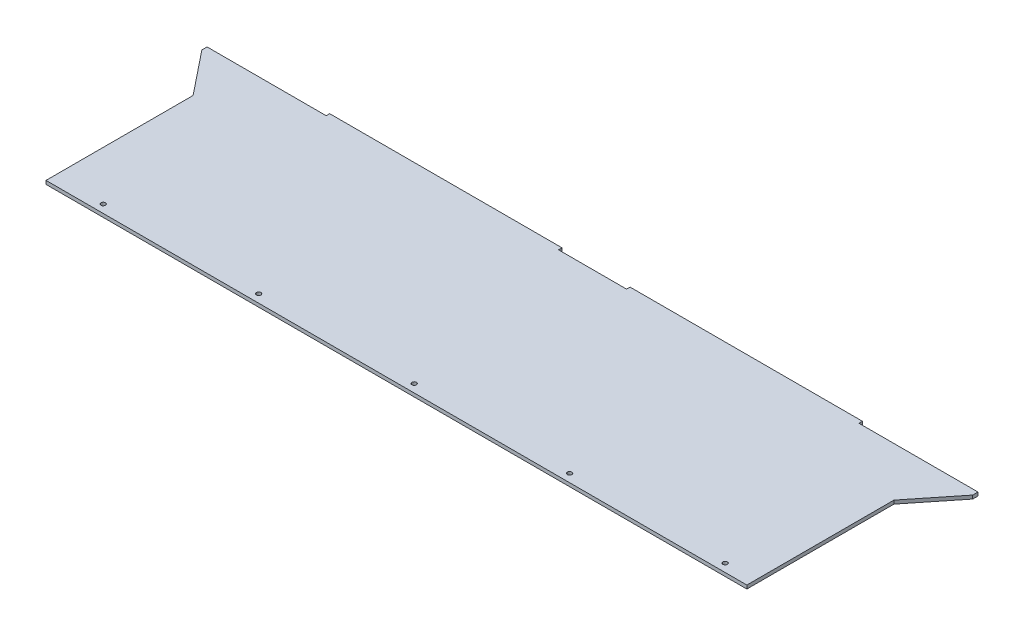
SolidWorks part; units mm, degrees
material "6061-T6 (SS)"
ref_plane "X-Y Datum" through (0, 0, 0) normal (0, 0, 1) x (1, 0, 0)
ref_plane "X-Z Datum" through (0, 0, 0) normal (0, 1, 0) x (1, 0, 0)
ref_plane "Y-Z Datum" through (0, 0, 0) normal (1, 0, 0) x (0, 0, -1)
sketch "Sketch1" plane through (0, 0, 0) normal (0, 1, 0) x (1, 0, 0)
  line L1 (-317.6778, 88.9) -> (317.6778, 88.9)
  line L2 (-317.6778, 88.9) -> (-317.6778, -88.9)
  line L3 (-317.6778, -88.9) -> (317.6778, -88.9)
  line L4 (317.6778, 88.9) -> (317.6778, -88.9)
  line L5 (-317.6778, 88.9) -> (317.6778, -88.9) construction
  line L6 (-317.6778, -88.9) -> (317.6778, 88.9) construction
  point P0 (0, 0)
  dimension "D1" = 635.3556
  dimension "D2" = 177.8
extrude "Boss-Extrude1" add sketch "Sketch1" along normal mid plane 3.175
sketch "Sketch2" plane through (0, 0, -88.9) normal (0, 0, -1) x (-1, 0, 0)
  line L0 (-241.4778, -1.5875) -> (-241.4778, 1.5875) construction
  line L1 (241.4778, -1.5875) -> (241.4778, 1.5875)
  line L2 (-241.4778, -1.5875) -> (-241.4778, 1.5875)
  line L3 (-241.4778, -1.5875) -> (-241.4778, 1.5875)
  line L4 (241.4778, -1.5875) -> (241.4778, 1.5875) construction
  line L5 (241.4778, -1.5875) -> (241.4778, 1.5875)
  line L20 (-317.6778, -1.5875) -> (317.6778, -1.5875) construction
  line L21 (-241.4778, -1.5875) -> (-30.8229, -1.5875)
  line L22 (30.8229, -1.5875) -> (241.4778, -1.5875)
  line L40 (30.8229, -1.5875) -> (30.8229, 1.5875)
  line L41 (30.8229, 1.5875) -> (241.4778, 1.5875)
  line L57 (-241.4778, 1.5875) -> (-30.8229, 1.5875)
  line L58 (-30.8229, 1.5875) -> (-30.8229, -1.5875)
  line M22 (-317.6778, -1.5875) -> (317.6778, -1.5875)
  line M24 (317.6778, 1.5875) -> (-317.6778, 1.5875)
extrude "Boss-Extrude2" add sketch "Sketch2" along normal blind 3.175 contours L58 L2 M24 M22 | L40 L1 M22 M24 region at (-136.1504, 0, -88.9) region at (136.1504, 0, -88.9)
sketch "Sketch3" plane through (0, 1.5875, 0) normal (0, 1, 0) x (1, 0, 0)
  line L0 (-317.6778, 88.9) -> (-349.4278, 88.9)
  line L1 (-349.4278, 88.9) -> (-349.4278, 84.1375)
  line L2 (-349.4278, 84.1375) -> (-317.6778, 44.45)
  line L3 (-317.6778, 88.9) -> (-317.6778, -88.9) construction
  line L16 (317.6778, -88.9) -> (317.6778, 88.9)
  line L17 (317.6778, 88.9) -> (241.4778, 88.9)
  line L18 (241.4778, 88.9) -> (241.4778, 92.075)
  line L19 (30.8229, 92.075) -> (30.8229, 88.9)
  line L20 (30.8229, 88.9) -> (-30.8229, 88.9)
  line L21 (-30.8229, 88.9) -> (-30.8229, 92.075)
  line L22 (-241.4778, 92.075) -> (-241.4778, 88.9)
  line L23 (-241.4778, 88.9) -> (-317.6778, 88.9)
  line L24 (241.4778, 92.075) -> (30.8229, 92.075)
  line L25 (241.4778, 92.075) -> (30.8229, 92.075)
  line L26 (-317.6778, 88.9) -> (-317.6778, -88.9)
  line L27 (-317.6778, -88.9) -> (317.6778, -88.9)
  line L38 (-317.6778, 88.9) -> (-317.6778, 44.45)
  line L40 (-30.8229, 92.075) -> (-241.4778, 92.075)
  line L41 (-30.8229, 92.075) -> (-241.4778, 92.075)
  line M26 (-317.6778, 88.9) -> (-317.6778, -88.9)
  dimension "D1" = 31.75
  dimension "D2" = 4.7625
  dimension "D3" = 44.45
  dimension "D4" = 0
extrude "Boss-Extrude3" add sketch "Sketch3" against normal blind 3.175 contours L1 L2 L0 M26 region at (-329.2853, 1.5875, -73.9297)
mirror "Mirror1" about plane through (0, 0, 0) normal (1, 0, 0) of "Boss-Extrude3"
sketch "Sketch4" plane through (0, 1.5875, 0) normal (0, 1, 0) x (1, 0, 0)
  line L0 (-273.2278, -88.9) -> (-273.2278, -81.534)
  line L1 (-317.6778, -88.9) -> (317.6778, -88.9) construction
  line L2 (-273.2278, -81.534) -> (-317.6778, -81.534)
  line L3 (-317.6778, 44.45) -> (-317.6778, -88.9) construction
  circle A0 centre (-273.2278, -81.534) radius 2.025
extrude "Cut-Extrude1" cut sketch "Sketch4" against normal blind 10 contours L0 A0 L2 | L2 A0 L0 region at (-274.0872, 1.5875, 82.3934) region at (-272.9413, 1.5875, 81.2475)
pattern_linear "LPattern1" count 5 spacing 140.97 along (1, 0, 0) of "Cut-Extrude1"
